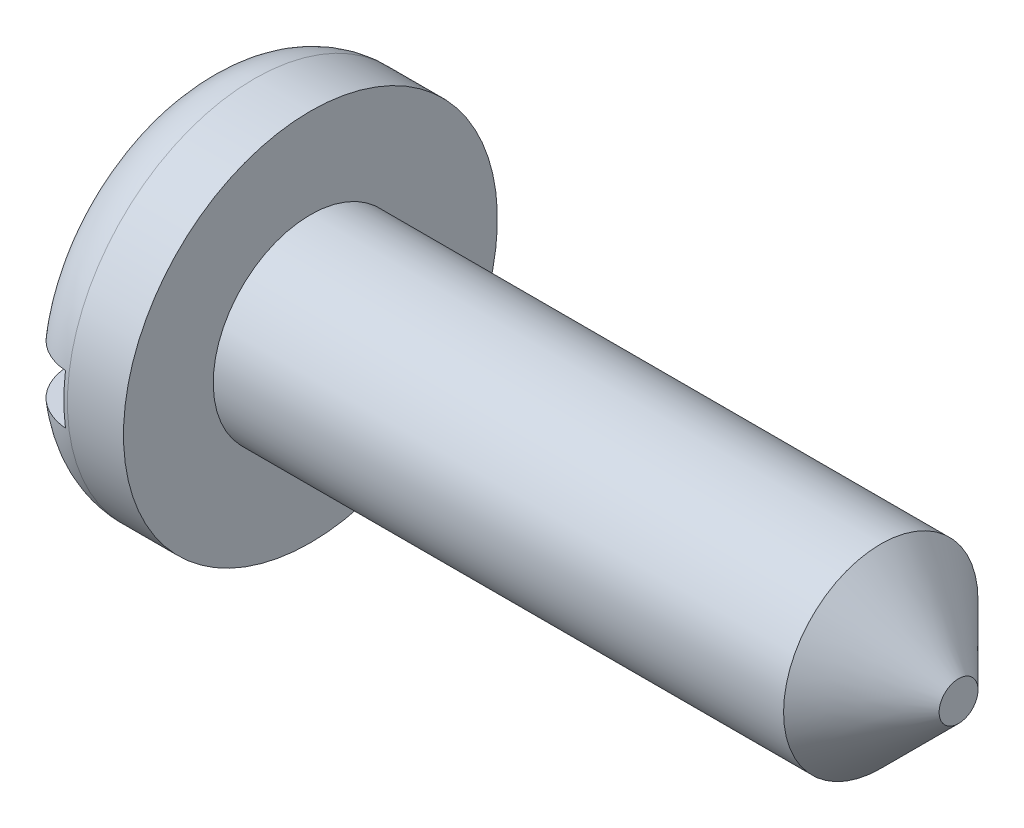
SolidWorks part; units mm, degrees
ref_plane "Front" through (0, 0, 0) normal (0, 0, 1) x (1, 0, 0)
ref_plane "Top" through (0, 0, 0) normal (0, 1, 0) x (1, 0, 0)
ref_plane "Right" through (0, 0, 0) normal (1, 0, 0) x (0, 0, -1)
ref_axis "Axis1" through (-84.4107, 0, 0) along (1, 0, 0)
ref_axis "Axis2" through (0, 64.3378, 0) along (0, -1, 0)
ref_axis "Axis3" through (0, 0, -102.329) along (0, 0, 1)
sketch "Sketch1" plane through (0, 0, 0) normal (0, 0, 1) x (1, 0, 0)
  line L0 (0, 0) -> (0, 2.625)
  line L1 (1.125, 3.75) -> (2.25, 3.75)
  line L2 (2.25, 3.75) -> (2.25, 1.95)
  line L3 (2.25, 1.95) -> (13.69, 1.95)
  line L4 (15.25, 0.39) -> (15.25, 0)
  line L5 (15.25, 0) -> (0, 0) construction
  line L6 (13.69, 1.95) -> (15.25, 0.39)
  line L7 (0, 0) -> (15.25, 0)
  arc A0 (0, 2.625) -> (1.125, 3.75) centre (1.125, 2.625) cw
  point P5 (15.25, 1.95)
  point P9 (0, 3.75)
revolve "Revolve1" add sketch "Sketch1" angle 360 about L5
sketch "Sketch2" plane through (0, 0, 0) normal (0, 0, 1) x (1, 0, 0)
  line L1 (0, 0.5) -> (1.05, 0.5)
  line L2 (0, 0.5) -> (0, -0.5)
  line L3 (0, -0.5) -> (1.05, -0.5)
  line L4 (1.05, 0.5) -> (1.05, -0.5)
  dimension "n" = 1
  dimension "t" = 1.05
extrude "Cut-Extrude1" cut sketch "Sketch2" against normal through all and the other way through all
equation "\"D3@Sketch1\" = \"k@Sketch1\"/2"
equation "\"D6@Sketch1\" = \"d1@Sketch1\"/2.5"
